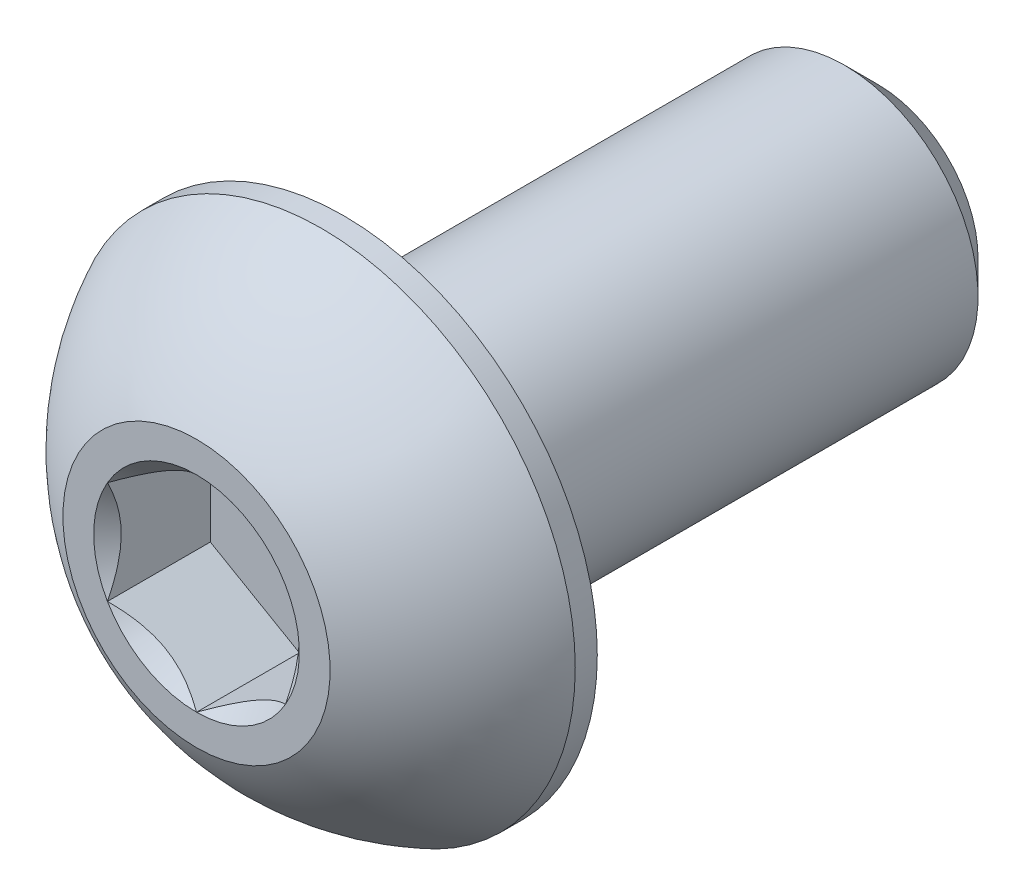
SolidWorks part; units mm, degrees
ref_plane "Front" through (0, 0, 0) normal (0, 0, 1) x (1, 0, 0)
ref_plane "Top" through (0, 0, 0) normal (0, 1, 0) x (1, 0, 0)
ref_plane "Right" through (0, 0, 0) normal (1, 0, 0) x (0, 0, -1)
sketch "Sketch1" plane through (0, 0, 0) normal (1, 0, 0) x (0, 0, -1)
  line L2 (1.65, 1.5) -> (7.65, 1.5)
  line L3 (7.65, 1.5) -> (7.65, 0)
  line L4 (7.65, 0) -> (1.65, 0)
  line L6 (1.4025, 2.85) -> (1.65, 2.85) construction
  line L7 (7.65, 1.5) -> (7.65, -1.5) construction
  line L8 (0, 0) -> (1.65, 0) construction
  line L9 (1.65, 2.85) -> (1.65, -2.85) construction
  line L11 (1.65, 1.5) -> (1.65, 0)
  line L13 (0, 1) -> (0, -1) construction
  line L14 (0, 1) -> (0, 1.5) construction
  arc A3 (0, 1.5) -> (1.4025, 2.85) centre (2.7948, 0) cw construction
  dimension "D1" = 0.2475
revolve "Revolve1" add sketch "Sketch1" angle 360 mid plane about L4
sketch "Sketch3" plane through (0, 0, -7.65) normal (0, 0, -1) x (-1, 0, 0)
  circle A0 centre (0, 0) radius 1.5
curve "Helix/Spiral1" pitch 0.5 height 6.5 turns 13
chamfer "Chamfer1" distance 0.375 angle 45 1 edges at (0, 1.5, -7.65)
sketch "Sketch7" plane through (0, 0, 0) normal (1, 0, 0) x (0, 0, -1)
  line L6 (1.4025, 2.85) -> (1.65, 2.85) construction
  line L8 (0, 0) -> (1.65, 0) construction
  line L11 (1.65, 2.85) -> (1.65, -2.85) construction
  line L12 (1.4025, 2.85) -> (1.65, 2.85)
  line L13 (0, 0) -> (1.65, 0)
  line L14 (0, 1) -> (0, -1) construction
  line L15 (1.65, 2.85) -> (1.65, 0)
  line L16 (0, 1.5) -> (0, 0)
  arc A2 (1.4025, 2.85) -> (0, 1.5) centre (2.7948, 0) ccw construction
  arc A3 (1.4025, 2.85) -> (0, 1.5) centre (2.7948, 0) ccw
revolve "Revolve2" add sketch "Sketch7" angle 360 mid plane about L13
sketch "Sketch5" plane through (0, 0, 0) normal (0, 0, 1) x (1, 0, 0)
  line L1 (1, -0.5774) -> (1, 0.5774)
  line L2 (1, 0.5774) -> (0, 1.1547)
  line L3 (0, 1.1547) -> (-1, 0.5774)
  line L4 (-1, 0.5774) -> (-1, -0.5774)
  line L5 (-1, -0.5774) -> (0, -1.1547)
  line L6 (0, -1.1547) -> (1, -0.5774)
  circle A0 centre (0, 0) radius 1 construction
extrude "Cut-Extrude2" cut sketch "Sketch5" against normal blind 1.155
sketch "Sketch6" plane through (0, 0, 0) normal (0, 0, 1) x (1, 0, 0)
  circle A0 centre (0, 0) radius 1.1547
extrude "Cut-Extrude3" cut sketch "Sketch6" against normal blind 1.155 draft 45
sketch "Sketch2" plane through (0, 0, 0) normal (1, 0, 0) x (0, 0, -1)
  line L0 (7.275, 1.5) -> (7.7125, 1.5)
  line L1 (7.7125, 1.5) -> (7.525, 1.1752)
  line L2 (7.525, 1.1752) -> (7.4625, 1.1752)
  line L3 (7.4625, 1.1752) -> (7.275, 1.5)
  line L4 (7.3688, 1.3376) -> (7.6188, 1.3376) construction
  dimension "D1" = 60
  dimension "D2" = 0.0625
  dimension "D3" = 0.25
sweep "Cut-Sweep1" [suppressed] cut profiles "Sketch2" path "Helix/Spiral1"
sketch "Sketch9" [suppressed] plane through (0, 0, -6.6) normal (0, 0, 1) x (1, 0, 0)
  circle A2 centre (0, 0) radius 6
extrude "Boss-Extrude2" [suppressed] add sketch "Sketch9" against normal offset from surface (19 mm away) 32
sketch "Sketch10" plane through (0, 0, 0) normal (1, 0, 0) x (0, 0, -1)
  line L0 (7.65, 1.5) -> (7.65, -1.5) construction
  point P0 (6.9, -1.5)
  dimension "D1" = 0.75
equation "\"D3@Helix/Spiral1\" = \"Lg@Sketch1\" + \"D4@Helix/Spiral1\""
equation "\"D2@Sketch2\" = \"D4@Helix/Spiral1\" * .125"
equation "\"D3@Sketch2\" = \"D4@Helix/Spiral1\" * .5"
equation "\"D1@Chamfer1\" = \"D4@Helix/Spiral1\" * .75"
equation "\"D1@Cut-Extrude2\" = \"Head Ht@Sketch1\" * .7"
equation "\"D1@Sketch1\" = \"Head Ht@Sketch1\" * .15"
equation "\"D1@Sketch10\" = \"D4@Helix/Spiral1\" * 1.5"
equation "\"D1@Cut-Extrude3\" = \"D1@Cut-Extrude2\""
